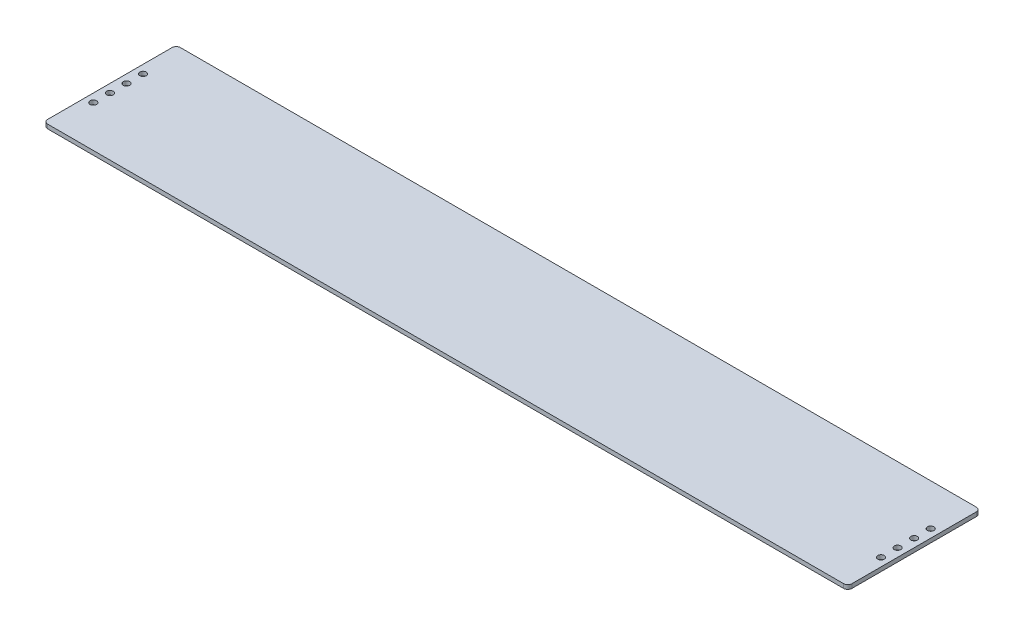
SolidWorks part; units mm, degrees
ref_plane "Front Plane" through (0, 0, 0) normal (0, 0, 1) x (1, 0, 0)
ref_plane "Top Plane" through (0, 0, 0) normal (0, 1, 0) x (1, 0, 0)
ref_plane "Right Plane" through (0, 0, 0) normal (1, 0, 0) x (0, 0, -1)
sketch "Sketch1" plane through (0, 0, 0) normal (0, 1, 0) x (1, 0, 0)
  line L0 (-301.625, 19.05) -> (-301.625, -19.05) construction
  line L1 (-307.975, -50.8) -> (307.975, -50.8)
  line L2 (-307.975, -50.8) -> (-307.975, 50.8)
  line L3 (-307.975, 50.8) -> (307.975, 50.8)
  line L4 (307.975, -50.8) -> (307.975, 50.8)
  line L5 (-307.975, -50.8) -> (307.975, 50.8) construction
  line L6 (-307.975, 50.8) -> (307.975, -50.8) construction
  line L7 (0, 50.8) -> (0, -50.8) construction
  circle A2 centre (-301.625, 19.05) radius 2.4892
  circle A3 centre (-301.625, 6.35) radius 2.4892
  circle A4 centre (-301.625, -6.35) radius 2.4892
  circle A5 centre (-301.625, -19.05) radius 2.4892
  circle A6 centre (301.625, -19.05) radius 2.4892
  circle A7 centre (301.625, -6.35) radius 2.4892
  circle A8 centre (301.625, 6.35) radius 2.4892
  circle A9 centre (301.625, 19.05) radius 2.4892
  point P0 (0, 0)
  point P8 (-301.625, 0)
  dimension "D3" = 6.35
  dimension "D4" = 4.9784
  dimension "D5" = 4
  dimension "D6" = 50.8
  dimension "D7" = 12.7
  dimension "D1" = 101.6
  dimension "D2" = 615.95
extrude "Boss-Extrude1" add sketch "Sketch1" along normal blind 3.175
fillet "Fillet1" radius 3.175 4 edges at (307.975, 1.5875, 50.8) (-307.975, 1.5875, -50.8) (307.975, 1.5875, -50.8) (-307.975, 1.5875, 50.8)
